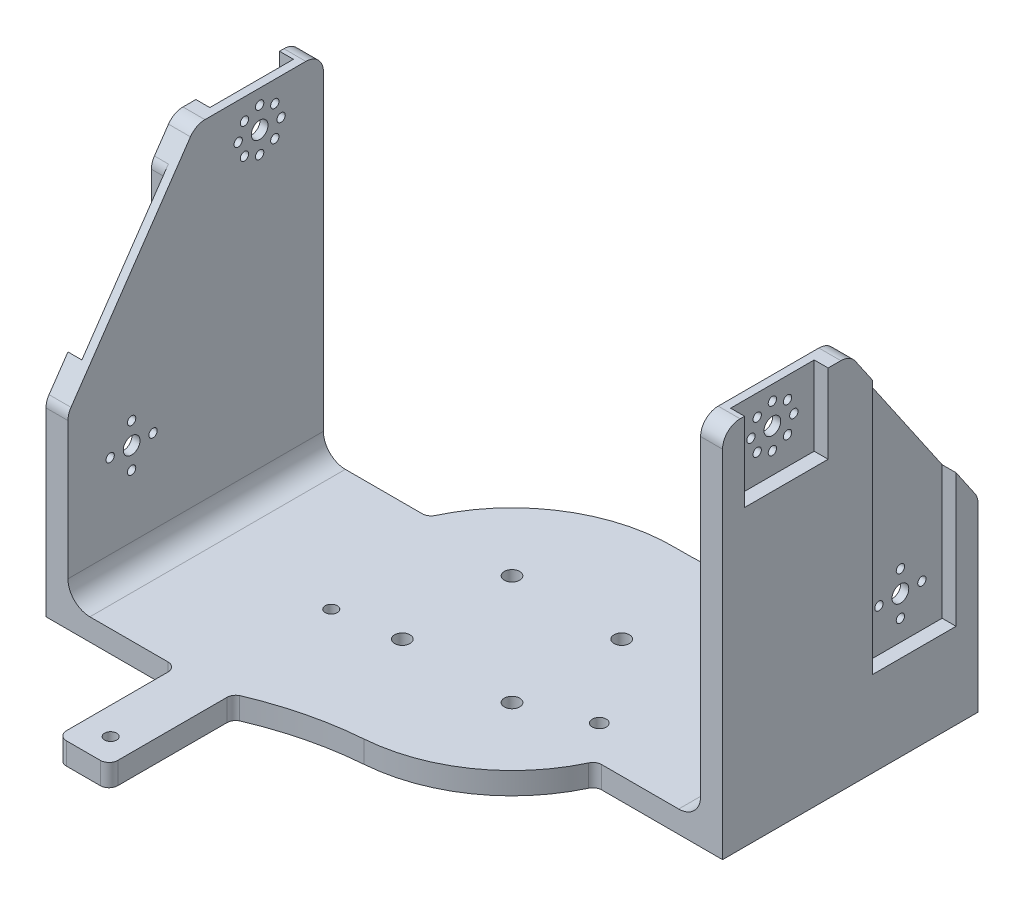
SolidWorks part; units mm, degrees
ref_plane "Front" through (0, 0, 0) normal (0, 0, 1) x (1, 0, 0)
ref_plane "Top" through (0, 0, 0) normal (0, 1, 0) x (1, 0, 0)
ref_plane "Right" through (0, 0, 0) normal (1, 0, 0) x (0, 0, -1)
sketch "Sketch2" plane through (0, 0, 0) normal (0, 1, 0) x (1, 0, 0)
  line L0 (0, 0) -> (0, -141.6255) construction
  line L1 (-115, -141.6255) -> (115, -141.6255)
  line L2 (-115, -141.6255) -> (-115, 141.6255)
  line L3 (-115, 141.6255) -> (115, 141.6255)
  line L4 (115, -141.6255) -> (115, 141.6255)
  line L5 (0, 0) -> (-115, 0) construction
  point P0 (0, 0)
  dimension "D1" = 283.251
  dimension "D2" = 230
extrude "Boss-Extrude1" add sketch "Sketch2" along normal blind 10
sketch "Sketch3" plane through (0, 0, 0) normal (0, 1, 0) x (1, 0, 0)
  line L0 (-115, -141.6255) -> (115, -141.6255) construction
  line L1 (-115, 141.6255) -> (-125, 141.6255)
  line L2 (-115, 141.6255) -> (-115, -141.6255)
  line L3 (-115, -141.6255) -> (-125, -141.6255)
  line L4 (-125, 141.6255) -> (-125, -141.6255)
  line L5 (0, 0) -> (0, 141.6255) construction
  line L6 (115, 141.6255) -> (-115, 141.6255) construction
  line L7 (125, 141.6255) -> (125, -141.6255)
  line L8 (115, -141.6255) -> (125, -141.6255)
  line L9 (115, 141.6255) -> (115, -141.6255)
  line L10 (115, 141.6255) -> (125, 141.6255)
  dimension "D1" = 10
extrude "Boss-Extrude2" add sketch "Sketch3" along normal blind 170
sketch "Sketch4" plane through (0, 10, 0) normal (0, 1, 0) x (1, 0, 0)
  point P4 (0, 0)
hole_wizard "M6 Clearance Hole1" positions "Sketch5" profile "Sketch6" hole size "M6" standard "ANSI Metric" end condition up to next
sketch "Sketch5" plane through (0, 10, 0) normal (0, 1, 0) x (1, 0, 0)
  line L0 (0, 0) -> (0, 25) construction
  line L1 (0, 25) -> (-25, 25) construction
  line L3 (0, 25) -> (25, 25) construction
  point P0 (-25, 25)
  point P13 (25, 25)
  point P14 (25, -25)
  point P15 (-25, -25)
  dimension "D1" = 25
  dimension "D2" = 4
sketch "Sketch6" plane through (-25, 10, -25) normal (1, 0, 0) x (0, 0, 1)
  line L0 (0, 0) -> (0, 10)
  line L1 (0, 10) -> (3.5, 10)
  line L2 (3.5, 10) -> (3.5, 0)
  line L5 (3.5, 0) -> (0, 0)
  line L11 (0, -6.35) -> (0, 107.95) construction
  dimension "Thru Hole Dia." = 7
  dimension "Thru Hole Depth" = 10
sketch "Sketch7" plane through (115, 0, 0) normal (-1, 0, 0) x (0, 0, 1)
  line L0 (-141.6255, 170) -> (141.6255, 170) construction
  line L1 (0, 153.49) -> (0, 163.269) construction
  line L2 (0, 153.49) -> (0, 163.269) construction
  circle A0 centre (0, 153.49) radius 3.81
  circle A1 centre (0, 163.269) radius 1.8987
  circle A2 centre (6.9148, 160.4048) radius 1.8987
  circle A3 centre (9.779, 153.49) radius 1.8987
  circle A4 centre (6.9148, 146.5752) radius 1.8987
  circle A5 centre (0, 143.711) radius 1.8987
  circle A6 centre (-6.9148, 146.5752) radius 1.8987
  circle A7 centre (-9.779, 153.49) radius 1.8987
  circle A8 centre (-6.9148, 160.4048) radius 1.8987
  point P7 (0, 170)
  dimension "D1" = 7.62
  dimension "D3" = 3.7973
  dimension "D2" = 16.51
  dimension "D6" = 9.779
  dimension "D5" = 8
extrude "Cut-Extrude1" cut sketch "Sketch7" against normal through all both and the other way through all
sketch "Sketch8" plane through (0, 170, 0) normal (0, 1, 0) x (1, 0, 0)
  line L1 (118.65, -19.05) -> (125, -19.05)
  line L2 (118.65, -19.05) -> (118.65, 19.05)
  line L3 (118.65, 19.05) -> (125, 19.05)
  line L4 (125, -19.05) -> (125, 19.05)
  line L5 (118.65, -19.05) -> (125, 19.05) construction
  line L6 (118.65, 19.05) -> (125, -19.05) construction
  line L9 (125, -141.6255) -> (125, 141.6255) construction
  line L10 (0, 0) -> (0, 141.6255) construction
  line L11 (115, 141.6255) -> (-115, 141.6255) construction
  line L13 (-118.65, 19.05) -> (-125, -19.05) construction
  line L14 (-118.65, -19.05) -> (-125, 19.05) construction
  line L16 (-125, -19.05) -> (-125, 19.05)
  line L17 (-118.65, 19.05) -> (-125, 19.05)
  line L18 (-118.65, -19.05) -> (-118.65, 19.05)
  line L19 (-118.65, -19.05) -> (-125, -19.05)
  point P0 (121.825, 0)
  point P12 (125, 0)
  point P23 (-121.825, 0)
  dimension "D1" = 38.1
  dimension "D2" = 6.35
extrude "Cut-Extrude2" cut sketch "Sketch8" against normal blind 36.025
sketch "Sketch9" plane through (125, 0, 0) normal (1, 0, 0) x (0, 0, -1)
  line L0 (41.831, 41.4022) -> (47.927, 41.4022) construction
  line L2 (77.351, 77.4302) -> (77.351, 38.9022)
  line L3 (77.351, 38.9022) -> (39.331, 38.9022)
  line L4 (39.331, 77.4302) -> (39.331, 38.9022)
  line L5 (77.351, 77.4302) -> (39.331, 38.9022) construction
  line L6 (77.351, 38.9022) -> (39.331, 77.4302) construction
  line L7 (41.831, 50.5462) -> (41.831, 41.4022) construction
  line L9 (39.331, 77.4302) -> (77.351, 77.4302) construction
  line L10 (39.331, 77.4302) -> (39.331, 170)
  line L11 (19.05, 170) -> (141.6255, 170) construction
  line L12 (39.331, 170) -> (77.351, 170)
  line L13 (77.351, 170) -> (77.351, 77.4302)
  point P0 (58.341, 58.1662)
  point P10 (58.341, 67.9452)
  point P11 (48.562, 58.1662)
  point P13 (58.341, 48.3872)
  point P15 (68.12, 58.1662)
  dimension "D1" = 2.5
  dimension "D2" = 2.5
extrude "Cut-Extrude3" cut sketch "Sketch9" against normal blind 6.35
sketch "Sketch11" plane through (118.65, 0, 0) normal (1, 0, 0) x (0, 0, -1)
  circle A0 centre (58.341, 58.1662) radius 3.81
  circle A1 centre (0, 153.49) radius 3.81 construction
extrude "Cut-Extrude4" cut sketch "Sketch11" against normal up to next
hole_wizard "#6 Clearance Hole1" positions "Sketch12" profile "Sketch13" hole size "#6" standard "ANSI Inch" end condition up to next
sketch "Sketch12" plane through (118.65, 0, 0) normal (1, 0, 0) x (0, 0, -1)
  point P0 (58.341, 67.9452)
  point P3 (48.562, 58.1662)
  point P6 (68.12, 58.1662)
  point P10 (58.341, 48.3872)
sketch "Sketch13" plane through (118.65, 67.9452, -58.341) normal (0, 1, 0) x (0, 0, -1)
  line L0 (0, 0) -> (0, 3.65)
  line L1 (0, 3.65) -> (1.8986, 3.65)
  line L2 (1.8986, 3.65) -> (1.8986, 0)
  line L5 (1.8986, 0) -> (0, 0)
  line L11 (0, -6.35) -> (0, 107.95) construction
  dimension "Thru Hole Dia." = 3.7973
  dimension "Thru Hole Depth" = 3.65
ref_plane "Plane1" through (0, 0, 0) normal (-0.7071, 0, 0.7071) x (0.7071, 0, 0.7071)
ref_axis "Axis1" through (0, 0, 0) along (0, 1, 0)
pattern_circular "CirPattern1" count 2 over 360 about axis through (0, 0, 0) along (0, 1, 0) of "Cut-Extrude3", "Cut-Extrude4", "#6 Clearance Hole1"
sketch "Esquisse1" plane through (0, 10, 0) normal (0, 1, 0) x (1, 0, 0)
  circle A0 centre (53, 87.3255) radius 3.175
  circle A1 centre (53, -13.2107) radius 3.175
  dimension "D1" = 6.35
  dimension "D2" = 6.35
extrude "Enlèv. mat.-Extru.1" cut sketch "Esquisse1" against normal up to next
sketch "Sketch17" plane through (0, 10, 0) normal (0, 1, 0) x (1, 0, 0)
  point P0 (-53, -29.3566)
  point P1 (-53, -129.8927)
hole_wizard "CBORE for M5 SHCS1" positions "Sketch18" profile "Sketch19" counterbore size "M5" standard "ANSI Metric" end condition through all
sketch "Sketch18" plane through (0, 0, 0) normal (0, -1, 0) x (-1, 0, 0)
  point P0 (53, -29.3566)
  point P3 (53, -129.8927)
sketch "Sketch19" plane through (-53, 0, 29.3566) normal (1, 0, 0) x (0, 0, -1)
  line L0 (0, 0) -> (0, 170)
  line L1 (0, 170) -> (2.75, 170)
  line L3 (2.75, 170) -> (2.75, 5)
  line L4 (2.75, 5) -> (5, 5)
  line L5 (5, 5) -> (5, 0)
  line L7 (5, 0) -> (0, 0)
  line L11 (0, -6.35) -> (0, 107.95) construction
  dimension "Thru Hole Dia." = 5.5
  dimension "Thru Hole Depth" = 170
  dimension "C'Bore Dia." = 10
  dimension "C'Bore Depth" = 5
sketch "Sketch15" plane through (0, 10, 0) normal (0, 1, 0) x (1, 0, 0)
  line L17 (115, 141.6255) -> (-115, 141.6255) construction
  line L23 (125, 141.6255) -> (-125, 141.6255)
  line L24 (-125, 141.6255) -> (-125, 29.05)
  line L25 (-125, 141.6255) -> (-125, 19.05) construction
  line L33 (-125, 29.05) -> (-67.3383, 29.05)
  line L34 (39.825, 100.5005) -> (66.175, 100.5005)
  line L36 (66.175, 100.5005) -> (66.175, 87.351)
  line L39 (66.175, 87.351) -> (125, 87.351)
  line L42 (125, 87.351) -> (125, 141.6255)
  line L45 (118.65, 77.351) -> (125, 77.351) construction
  line L46 (39.825, 61.5818) -> (39.825, 100.5005)
  line L48 (125, -141.6255) -> (125, -29.05)
  line L49 (125, -29.05) -> (67.3383, -29.05)
  line L52 (-66.175, -87.351) -> (-125, -87.351)
  line L53 (-125, -87.351) -> (-125, -141.6255)
  line L56 (-66.175, -87.351) -> (-66.175, -141.6255)
  line L57 (-39.825, -100.5005) -> (-66.175, -100.5005) [skipped]
  line L58 (-39.825, -61.5818) -> (-39.825, -100.5005) [skipped]
  line L59 (-66.175, -100.5005) -> (-66.175, -87.351) [skipped]
  line L60 (-39.825, -61.5818) -> (-39.825, -141.6255)
  line L61 (-125, -141.6255) -> (125, -141.6255) [skipped]
  line L62 (-115, -141.6255) -> (115, -141.6255) construction
  line L63 (-39.825, -141.6255) -> (125, -141.6255)
  line L64 (-66.175, -141.6255) -> (-125, -141.6255)
  circle A0 centre (0, 0) radius 73.3372 construction
  circle A1 centre (-53, -29.3566) radius 2.75 construction
  circle A2 centre (53, 87.3255) radius 3.175 construction
  arc A3 (-67.3383, 29.05) -> (39.825, 61.5818) centre (0, 0) cw
  arc A5 (67.3383, -29.05) -> (-39.825, -61.5818) centre (0, 0) cw
  point P34 (0, 0)
  dimension "D1" = 10
  dimension "D3" = 10
  dimension "D4" = 10
  dimension "D5" = 10
  dimension "D2" = 10
  dimension "D6" = 10
  dimension "D7" = 2
extrude "Cut-Extrude5" cut sketch "Sketch15" against normal through all both and the other way through all
sketch "Sketch20" plane through (0, 10, 0) normal (0, 1, 0) x (1, 0, 0)
  line L0 (-65.41, -87.351) -> (-66.175, -87.351)
  line L1 (-65.41, -118.5943) -> (-65.41, -85.0627) construction
  line L2 (-65.41, -87.351) -> (-65.41, -141.6255)
  line L3 (-65.41, -141.6255) -> (-66.175, -141.6255)
  line L4 (-66.175, -141.6255) -> (-66.175, -87.351)
  line L7 (-66.175, -141.6255) -> (-39.825, -141.6255) construction
  line L8 (-39.825, -141.6255) -> (-39.825, -84.3349)
  line L9 (-39.825, -141.6255) -> (-39.825, -61.5818) construction
  line L10 (-41.9959, -87.8922) -> (-41.9959, -141.6255)
  line L11 (39.825, 100.5005) -> (66.175, 100.5005)
  line L13 (-41.9959, -141.6255) -> (-39.825, -141.6255)
  line L14 (66.175, 100.5005) -> (39.825, 100.5005) construction
  line L16 (39.825, 100.5005) -> (39.825, 61.5818) construction
  line L17 (39.825, 77.6106) -> (39.825, 100.5005)
  line L18 (66.175, 100.5005) -> (66.175, 87.351)
  line L19 (66.175, 87.351) -> (65.41, 87.351)
  line L23 (42, 81.17) -> (42, 93.17)
  line L24 (46, 97.17) -> (61.41, 97.17)
  line L25 (65.41, 93.17) -> (65.41, 87.351)
  arc A2 (-37.9959, -83.8922) -> (-41.9959, -87.8922) centre (-37.9959, -87.8922) ccw construction
  arc A3 (-41.9959, -87.8922) -> (-39.825, -84.3349) centre (-37.9959, -87.8922) cw
  arc A6 (42, 81.17) -> (39.825, 77.6106) centre (38, 81.17) cw
  arc A7 (38, 77.17) -> (42, 81.17) centre (38, 81.17) ccw construction
  arc A8 (42, 93.17) -> (46, 97.17) centre (46, 93.17) cw
  arc A9 (61.41, 97.17) -> (65.41, 93.17) centre (61.41, 93.17) cw
extrude "Cut-Extrude7" cut sketch "Sketch20" against normal through all both and the other way through all
fillet "Fillet2" radius 4 2 edges at (-41.9959, 5, 141.6255) (-65.41, 5, 141.6255)
fillet "Fillet3" radius 144 2 edges at (39.825, 5, -61.5818) (-39.825, 5, 61.5818)
fillet "Fillet4" radius 4 4 edges at (65.41, 5, -87.351) (-67.3383, 5, -29.05) (67.3383, 5, 29.05) (-65.41, 5, 87.351)
sketch "Sketch22" plane through (-125, 0, 0) normal (-1, 0, 0) x (0, 0, 1)
  line L0 (29.1505, 170) -> (87.351, 84.9272)
  line L1 (19.05, 170) -> (39.331, 170) construction
  line L2 (87.351, 0) -> (87.351, 170) construction
  line L3 (77.351, 74.9272) -> (87.351, 74.9272) construction
  line L4 (87.351, 74.9272) -> (87.351, 84.9272) construction
  line L5 (19.05, 170) -> (29.1505, 170) construction
  line L6 (-19.05, 170) -> (-29.1505, 170) construction
  line L7 (-87.351, 170) -> (29.05, 170) construction
  line L8 (29.1505, 170) -> (87.351, 170)
  line L9 (87.351, 170) -> (87.351, 84.9272)
  line L10 (19.05, 133.975) -> (19.05, 170) construction
  line L11 (77.351, 38.9022) -> (77.351, 74.9272) construction
extrude "Cut-Extrude8" cut sketch "Sketch22" against normal up to next
sketch "Sketch23" plane through (125, 0, 0) normal (1, 0, 0) x (0, 0, -1)
  line L0 (19.05, 170) -> (29.05, 170) construction
  line L1 (19.05, 170) -> (39.331, 170) construction
  line L2 (29.05, 170) -> (87.351, 84.9272)
  line L3 (87.351, 0) -> (87.351, 170) construction
  line L4 (87.351, 84.9272) -> (87.351, 74.9272) construction
  line L5 (87.351, 74.9272) -> (77.351, 74.9272) construction
  line L6 (-19.05, 170) -> (-29.05, 170) construction
  line L7 (87.351, 84.9272) -> (87.351, 170)
  line L8 (87.351, 170) -> (29.05, 170)
  line L9 (77.351, 38.9022) -> (77.351, 74.9272) construction
  line L10 (19.05, 133.975) -> (19.05, 170) construction
extrude "Cut-Extrude9" cut sketch "Sketch23" against normal up to next
fillet "Fillet5" radius 8 6 edges at (120, 84.9272, -87.351) (120, 170, -29.05) (-120, 170, -29.05) (120, 170, 29.05) (-120, 170, 29.1505) (-120, 84.9272, 87.351)
split "Split1" [suppressed] bodies to split 136
fillet "Fillet6" radius 8 1 edges at (-121.825, 155.119, 39.331)
fillet "Fillet7" radius 10 2 edges at (115, 10, -29.1505) (-115, 10, 29.1505)
equation "\"Longueur\"= 230"
equation "\"D2@Sketch2\"=\"Longueur\""
equation "\"Largeur\"= 280 + 2 * 1.6255mm"
equation "\"D1@Sketch2\"=\"Largeur\""
equation "\"D1@Sketch9\"=\"D2@Sketch9\""
